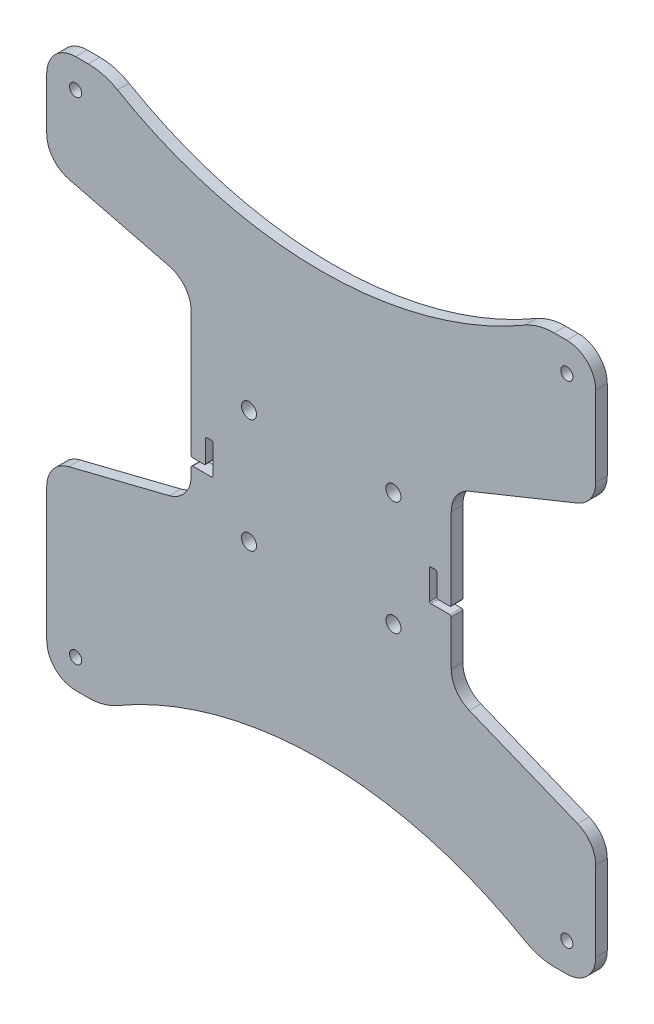
SolidWorks part; units mm, degrees
ref_plane "Front Plane" through (0, 0, 0) normal (0, 0, 1) x (1, 0, 0)
ref_plane "Top Plane" through (0, 0, 0) normal (0, 1, 0) x (1, 0, 0)
ref_plane "Right Plane" through (0, 0, 0) normal (1, 0, 0) x (0, 0, -1)
ref_plane "Plane1" through (0, 0, 0) normal (0, 0, -1) x (-1, 0, 0)
sketch "Sketch1" plane through (0, 0, 0) normal (0, 0, -1) x (-1, 0, 0)
  line L0 (87.4254, -29.1063) -> (52.5746, -20.3937)
  line L1 (45, -10.6922) -> (45, -8)
  line L2 (44.5, -7.5) -> (38, -7.5)
  line L3 (37.5, -7) -> (37.5, 3)
  line L4 (38, 3.5) -> (39.5, 3.5)
  line L5 (40, 3) -> (40, -4.5)
  line L6 (40.5, -5) -> (44.5, -5)
  line L7 (45, -4.5) -> (45, 38.6922)
  line L8 (52.5746, 48.3937) -> (87.4254, 57.1063)
  line L9 (95, 66.8078) -> (95, 85)
  line L10 (85, 95) -> (80.6, 95)
  line L11 (-80.6, 95) -> (-85, 95)
  line L12 (-95, 85) -> (-95, 57.3099)
  line L13 (-88.7544, 48.0415) -> (-51.2456, 32.8477)
  line L14 (-45, 23.5792) -> (-45, -4.5)
  line L15 (-44.5, -5) -> (-40.5, -5)
  line L16 (-40, -4.5) -> (-40, 3)
  line L17 (-39.5, 3.5) -> (-38, 3.5)
  line L18 (-37.5, 3) -> (-37.5, -7)
  line L19 (-38, -7.5) -> (-44.5, -7.5)
  line L20 (-45, -8) -> (-45, -23.5792)
  line L21 (-51.2456, -32.8477) -> (-88.7544, -48.0415)
  line L22 (-95, -57.3099) -> (-95, -85)
  line L23 (-85, -95) -> (-80.6, -95)
  line L24 (80.6, -95) -> (85, -95)
  line L25 (95, -85) -> (95, -38.8078)
  circle A0 centre (-85, -85) radius 2.1
  circle A1 centre (-85, 85) radius 2.1
  circle A2 centre (85, 85) radius 2.1
  circle A3 centre (85, -85) radius 2.1
  circle A4 centre (25, 19.0063) radius 2.6
  circle A5 centre (25, -20.3937) radius 2.6
  circle A6 centre (-25, -20.1) radius 2.6
  circle A7 centre (-25, 19.3) radius 2.6
  arc A8 (52.5746, -20.3937) -> (45, -10.6922) centre (55, -10.6922) cw
  arc A9 (45, -8) -> (44.5, -7.5) centre (44.5, -8) ccw
  arc A10 (38, -7.5) -> (37.5, -7) centre (38, -7) cw
  arc A11 (37.5, 3) -> (38, 3.5) centre (38, 3) cw
  arc A12 (39.5, 3.5) -> (40, 3) centre (39.5, 3) cw
  arc A13 (40, -4.5) -> (40.5, -5) centre (40.5, -4.5) ccw
  arc A14 (44.5, -5) -> (45, -4.5) centre (44.5, -4.5) ccw
  arc A15 (45, 38.6922) -> (52.5746, 48.3937) centre (55, 38.6922) cw
  arc A16 (87.4254, 57.1063) -> (95, 66.8078) centre (85, 66.8078) ccw
  arc A17 (95, 85) -> (85, 95) centre (85, 85) ccw
  arc A18 (80.6, 95) -> (70.525, 92.277) centre (80.6, 75) ccw
  arc A19 (70.525, 92.277) -> (-70.525, 92.277) centre (0, 213.2159) cw
  arc A20 (-70.525, 92.277) -> (-80.6, 95) centre (-80.6, 75) ccw
  arc A21 (-85, 95) -> (-95, 85) centre (-85, 85) ccw
  arc A22 (-95, 57.3099) -> (-88.7544, 48.0415) centre (-85, 57.3099) ccw
  arc A23 (-51.2456, 32.8477) -> (-45, 23.5792) centre (-55, 23.5792) cw
  arc A24 (-45, -4.5) -> (-44.5, -5) centre (-44.5, -4.5) ccw
  arc A25 (-40.5, -5) -> (-40, -4.5) centre (-40.5, -4.5) ccw
  arc A26 (-40, 3) -> (-39.5, 3.5) centre (-39.5, 3) cw
  arc A27 (-38, 3.5) -> (-37.5, 3) centre (-38, 3) cw
  arc A28 (-37.5, -7) -> (-38, -7.5) centre (-38, -7) cw
  arc A29 (-44.5, -7.5) -> (-45, -8) centre (-44.5, -8) ccw
  arc A30 (-45, -23.5792) -> (-51.2456, -32.8477) centre (-55, -23.5792) cw
  arc A31 (-88.7544, -48.0415) -> (-95, -57.3099) centre (-85, -57.3099) ccw
  arc A32 (-95, -85) -> (-85, -95) centre (-85, -85) ccw
  arc A33 (-80.6, -95) -> (-70.525, -92.277) centre (-80.6, -75) ccw
  arc A34 (-70.525, -92.277) -> (70.525, -92.277) centre (0, -213.2159) cw
  arc A35 (70.525, -92.277) -> (80.6, -95) centre (80.6, -75) ccw
  arc A36 (85, -95) -> (95, -85) centre (85, -85) ccw
  arc A37 (95, -38.8078) -> (87.4254, -29.1063) centre (85, -38.8078) ccw
  point P98 (-13, -20.1)
  point P99 (27, -20.3937)
  dimension "D1" = 39.4
  dimension "D5" = 5.2
  dimension "D6" = 4.2
  dimension "D2" = 39.4
  dimension "D3" = 20
  dimension "D4" = 20
extrude "Boss-Extrude1" add sketch "Sketch1" against normal blind 4
